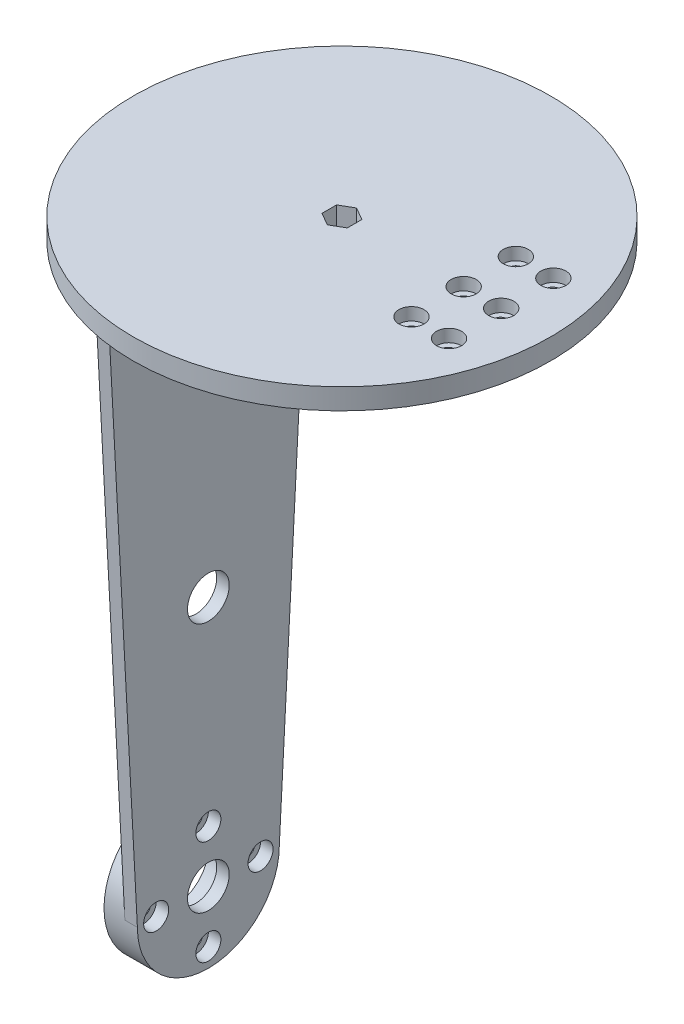
SolidWorks part; units mm, degrees
ref_plane "Front Plane" through (0, 0, 0) normal (0, 0, 1) x (1, 0, 0)
ref_plane "Top Plane" through (0, 0, 0) normal (0, 1, 0) x (1, 0, 0)
ref_plane "Right Plane" through (0, 0, 0) normal (1, 0, 0) x (0, 0, -1)
sketch "Sketch2" plane through (0, 0, 0) normal (0, 1, 0) x (1, 0, 0)
  circle A0 centre (0, 0) radius 7.5
extrude "Boss-Extrude1" add sketch "Sketch2" along normal blind 20
sketch "Sketch3" plane through (0, 20, 0) normal (0, 1, 0) x (1, 0, 0)
  line L3 (0, 3.5) -> (-3.0311, 1.75)
  line L4 (-3.0311, 1.75) -> (-3.0311, -1.75)
  line L5 (-3.0311, -1.75) -> (0, -3.5)
  line L6 (0, -3.5) -> (3.0311, -1.75)
  line L7 (3.0311, -1.75) -> (3.0311, 1.75)
  line L8 (3.0311, 1.75) -> (0, 3.5)
  point P6 (0, 0)
  point P9 (0, 0)
  point P11 (0, 0)
extrude "Cut-Extrude1" cut sketch "Sketch3" against normal blind 20
sketch "Sketch4" plane through (0, 20, 0) normal (0, 1, 0) x (1, 0, 0)
  circle A0 centre (0, 0) radius 50
  circle A1 centre (0, 0) radius 3.9955
extrude "Boss-Extrude3" add sketch "Sketch4" against normal blind 5
ref_plane "Plane3" through (0, 0, 0) normal (0.5, 0, 0.866) x (0.866, 0, -0.5)
sketch "Sketch11" plane through (0, 0, 0) normal (0.5, 0, 0.866) x (0.866, 0, -0.5)
  line L2 (0, 0) -> (0, 3) construction
  circle A0 centre (0, 3) radius 1.55
extrude "Cut-Extrude2" cut sketch "Sketch11" against normal blind 7.5 and the other way blind 7.5
ref_plane "Plane4" through (0, 0, 0) normal (1, 0, 0) x (0, 0, -1)
sketch "Sketch15" plane through (0, 0, 0) normal (1, 0, 0) x (0, 0, -1)
  circle A0 centre (0, 9) radius 1.55
extrude "Cut-Extrude9" cut sketch "Sketch15" against normal blind 7.5 and the other way blind 7.5
sketch "Sketch16" plane through (0, 15, 0) normal (0, -1, 0) x (1, 0, 0)
  line L0 (0, 0) -> (32, 0) construction
  line L6 (0, 0) -> (-32, 0) construction
  line L7 (-32, -25) -> (-32, 25) construction
  line L8 (32, 25) -> (32, -25) construction
  line L9 (32, 25) -> (35, 25) construction
  line L10 (32, -25) -> (35, -25) construction
  line L11 (35, 25) -> (35, -25) construction
  line L12 (32, 25) -> (35, -25) construction
  line L13 (32, -25) -> (35, 25) construction
  line L14 (32, 25) -> (26.3083, 25) construction
  line L15 (35, 25) -> (41, 25) construction
  line L16 (29.1541, 25) -> (29.1541, 12.5) construction
  line L17 (29.1541, 12.5) -> (29.1541, 0) construction
  line L18 (29.1541, 0) -> (29.1541, -12.5) construction
  line L19 (38, 25) -> (38, 12.5) construction
  line L20 (38, 12.5) -> (38, 0) construction
  line L21 (38, 0) -> (38, -12.5) construction
  circle A0 centre (29.1541, 12.5) radius 1.55
  circle A1 centre (29.1541, 0) radius 1.55
  circle A2 centre (29.1541, -12.5) radius 1.55
  circle A3 centre (38, -12.5) radius 1.55
  circle A4 centre (38, 0) radius 1.55
  circle A5 centre (38, 12.5) radius 1.55
  point P8 (32, 0)
  point P10 (-32, 0)
  point P14 (33.5, 0)
ref_plane "Plane7" through (-32, 0, 0) normal (-1, 0, 0) x (0, 0, 1)
sketch "Sketch28" plane through (-32, 0, 0) normal (-1, 0, 0) x (0, 0, 1)
  line L0 (25, 15) -> (-25, 15)
  line L1 (0, -135) -> (0, -75) construction
  line L2 (-50, 15) -> (50, 15) construction
  line L3 (0, 15) -> (0, -135) construction
  line L6 (25, 15) -> (17, -135)
  line L7 (-17, -135) -> (-25, 15)
  circle A0 centre (0, -135) radius 5
  arc A2 (-17, -135) -> (17, -135) centre (0, -135) ccw
  circle A3 centre (0, -75) radius 5
  point P4 (0, 15)
extrude "Boss-Extrude10" add sketch "Sketch28" along normal blind 3
sketch "Sketch25" plane through (-35, 0, 0) normal (-1, 0, 0) x (0, 0, 1)
  circle A6 centre (0, -135) radius 8
  circle A7 centre (0, -135) radius 17
extrude "Boss-Extrude8" add sketch "Sketch25" along normal blind 5
sketch "Sketch26" plane through (-40, 0, 0) normal (-1, 0, 0) x (0, 0, 1)
  circle A12 centre (0, -135) radius 12.5 construction
  circle A16 centre (-12.5, -135) radius 1.55
  circle A17 centre (0, -122.5) radius 1.55
  circle A18 centre (12.5, -135) radius 1.55
  circle A19 centre (0, -147.5) radius 1.55
  point P14 (0, -135)
extrude "Cut-Extrude14" cut sketch "Sketch26" against normal blind 8
sketch "Sketch27" plane through (-32, 0, 0) normal (1, 0, 0) x (0, 0, -1)
  circle A4 centre (0, -135) radius 12.5 construction
  circle A5 centre (-12.5, -135) radius 3
  circle A6 centre (0, -122.5) radius 3
  circle A7 centre (12.5, -135) radius 3
  circle A8 centre (0, -147.5) radius 3
  point P15 (0, -135)
extrude "Cut-Extrude15" cut sketch "Sketch27" against normal blind 3
extrude "Cut-Extrude17" cut sketch "Sketch16" against normal blind 5
sketch "Sketch29" plane through (0, 20, 0) normal (0, 1, 0) x (1, 0, 0)
  circle A0 centre (29.1541, 12.5) radius 3
  circle A1 centre (38.1541, 12.5) radius 3
  circle A2 centre (38.1541, 0) radius 3
  circle A3 centre (38.1541, -12.5) radius 3
  circle A4 centre (29.1541, 0) radius 3
  circle A5 centre (29.1541, -12.5) radius 3
  dimension "D1" = 2
  dimension "D2" = 3
extrude "Cut-Extrude18" cut sketch "Sketch29" against normal blind 3
